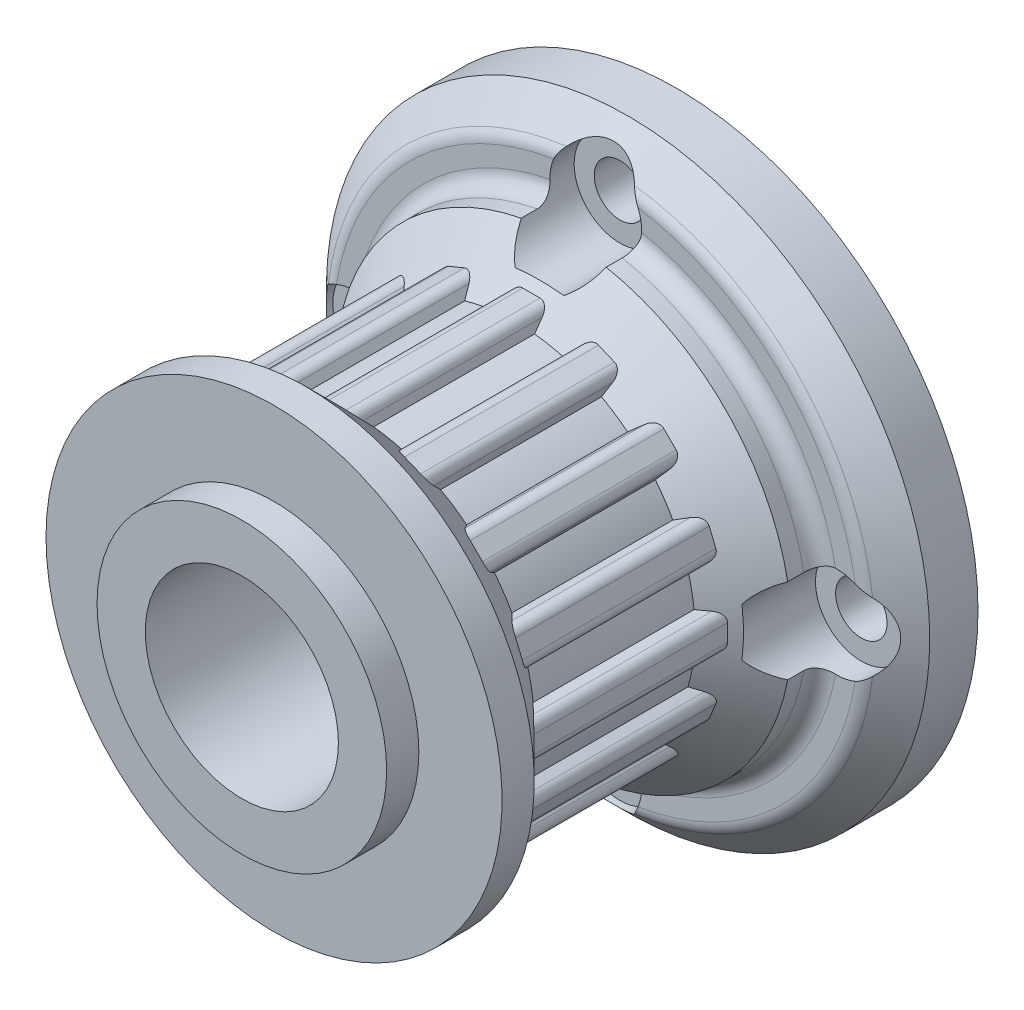
SolidWorks part; units mm, degrees
material "ABS"
ref_plane "Plan de face" through (0, 0, 0) normal (0, 0, 1) x (1, 0, 0)
ref_plane "Plan de dessus" through (0, 0, 0) normal (0, 1, 0) x (1, 0, 0)
ref_plane "Plan de droite" through (0, 0, 0) normal (1, 0, 0) x (0, 0, -1)
sketch "Esquisse5" plane through (0, 0, 0) normal (0, 0, 1) x (1, 0, 0)
  line L0 (0, 0) -> (0, 12.73) construction
  line L1 (0, 0) -> (4.8716, 11.761) construction
  line L2 (0, 12.1872) -> (0.5089, 12.1872)
  line L3 (1.1017, 11.6799) -> (1.2239, 10.8985)
  line L4 (1.2239, 10.8985) -> (2.9901, 10.5515)
  line L5 (2.9901, 10.5515) -> (3.3975, 11.2265)
  line L6 (4.1408, 11.4708) -> (4.6619, 11.2549)
  line L7 (0, 0) -> (2.107, 10.725) construction
  line L8 (4.6619, 11.2549) -> (5.1321, 11.0601)
  line L9 (5.4856, 10.3646) -> (5.2995, 9.5959)
  line L10 (5.2995, 9.5959) -> (6.7985, 8.5995)
  line L11 (6.7985, 8.5995) -> (7.4332, 9.0671)
  line L12 (8.2134, 9.0084) -> (8.6122, 8.6095)
  line L13 (8.6122, 8.6095) -> (8.9721, 8.2497)
  line L14 (9.0325, 7.4718) -> (8.5664, 6.8329)
  line L15 (8.5664, 6.8329) -> (9.57, 5.3386)
  line L16 (9.57, 5.3386) -> (10.3353, 5.5278)
  line L17 (11.0336, 5.1749) -> (11.2495, 4.6538)
  line L18 (11.2495, 4.6538) -> (11.4442, 4.1836)
  line L19 (11.2024, 3.4418) -> (10.5272, 3.03)
  line L20 (10.5272, 3.03) -> (10.8826, 1.2654)
  line L21 (10.8826, 1.2654) -> (11.6621, 1.1473)
  line L22 (12.1722, 0.554) -> (12.1722, -0.01)
  line L23 (12.1722, -0.01) -> (12.1722, -0.5189)
  line L24 (11.6649, -1.1117) -> (10.8835, -1.2339)
  line L25 (10.8835, -1.2339) -> (10.5365, -3.0001)
  line L26 (10.5365, -3.0001) -> (11.2115, -3.4075)
  line L27 (11.4558, -4.1508) -> (11.2399, -4.6719)
  line L28 (11.2399, -4.6719) -> (11.0452, -5.1421)
  line L29 (10.3496, -5.4957) -> (9.581, -5.3095)
  line L30 (9.581, -5.3095) -> (8.5845, -6.8085)
  line L31 (8.5845, -6.8085) -> (9.0522, -7.4432)
  line L32 (8.9934, -8.2234) -> (8.5946, -8.6222)
  line L33 (8.5946, -8.6222) -> (8.2347, -8.9821)
  line L34 (7.4568, -9.0425) -> (6.8179, -8.5764)
  line L35 (6.8179, -8.5764) -> (5.3236, -9.58)
  line L36 (5.3236, -9.58) -> (5.5128, -10.3453)
  line L37 (5.16, -11.0436) -> (4.6389, -11.2595)
  line L38 (4.6389, -11.2595) -> (4.1687, -11.4542)
  line L39 (3.4269, -11.2124) -> (3.015, -10.5372)
  line L40 (3.015, -10.5372) -> (1.2504, -10.8926)
  line L41 (1.2504, -10.8926) -> (1.1323, -11.6721)
  line L42 (0.5391, -12.1822) -> (-0.025, -12.1822)
  line L43 (-0.025, -12.1822) -> (-0.5339, -12.1822)
  line L44 (-1.1267, -11.6749) -> (-1.2489, -10.8935)
  line L45 (-1.2489, -10.8935) -> (-3.0151, -10.5465)
  line L46 (-3.0151, -10.5465) -> (-3.4225, -11.2215)
  line L47 (-4.1658, -11.4658) -> (-4.6869, -11.2499)
  line L48 (-4.6869, -11.2499) -> (-5.1571, -11.0552)
  line L49 (-5.5106, -10.3596) -> (-5.3245, -9.591)
  line L50 (-5.3245, -9.591) -> (-6.8235, -8.5945)
  line L51 (-6.8235, -8.5945) -> (-7.4582, -9.0622)
  line L52 (-8.2384, -9.0034) -> (-8.6372, -8.6046)
  line L53 (-8.6372, -8.6046) -> (-8.9971, -8.2447)
  line L54 (-9.0575, -7.4668) -> (-8.5914, -6.8279)
  line L55 (-8.5914, -6.8279) -> (-9.5949, -5.3336)
  line L56 (-9.5949, -5.3336) -> (-10.3603, -5.5228)
  line L57 (-11.0586, -5.17) -> (-11.2745, -4.6489)
  line L58 (-11.2745, -4.6489) -> (-11.4692, -4.1787)
  line L59 (-11.2274, -3.4369) -> (-10.5522, -3.025)
  line L60 (-10.5522, -3.025) -> (-10.9076, -1.2604)
  line L61 (-10.9076, -1.2604) -> (-11.6871, -1.1423)
  line L62 (-12.1972, -0.5491) -> (-12.1972, 0.015)
  line L63 (-12.1972, 0.015) -> (-12.1972, 0.5239)
  line L64 (-11.6899, 1.1167) -> (-10.9085, 1.2389)
  line L65 (-10.9085, 1.2389) -> (-10.5615, 3.0051)
  line L66 (-10.5615, 3.0051) -> (-11.2365, 3.4125)
  line L67 (-11.4808, 4.1558) -> (-11.2649, 4.6769)
  line L68 (-11.2649, 4.6769) -> (-11.0702, 5.1471)
  line L69 (-10.3746, 5.5006) -> (-9.6059, 5.3145)
  line L70 (-9.6059, 5.3145) -> (-8.6095, 6.8135)
  line L71 (-8.6095, 6.8135) -> (-9.0772, 7.4482)
  line L72 (-9.0184, 8.2284) -> (-8.6195, 8.6272)
  line L73 (-8.6195, 8.6272) -> (-8.2597, 8.9871)
  line L74 (-7.4818, 9.0475) -> (-6.8429, 8.5814)
  line L75 (-6.8429, 8.5814) -> (-5.3486, 9.5849)
  line L76 (-5.3486, 9.5849) -> (-5.5378, 10.3503)
  line L77 (-5.185, 11.0486) -> (-4.6638, 11.2645)
  line L78 (-4.6638, 11.2645) -> (-4.1937, 11.4592)
  line L79 (-3.4518, 11.2174) -> (-3.04, 10.5422)
  line L80 (-3.04, 10.5422) -> (-1.2754, 10.8975)
  line L81 (-1.2754, 10.8975) -> (-1.1573, 11.6771)
  line L82 (-0.5641, 12.1872) -> (0, 12.1872)
  circle A0 centre (0, 0) radius 12.73 construction
  circle A1 centre (0, 0) radius 12.23 construction
  circle A2 centre (0, 0) radius 10.93 construction
  arc A3 (4.1408, 11.4708) -> (3.3975, 11.2265) centre (3.9112, 10.9164) ccw
  arc A4 (1.1017, 11.6799) -> (0.5089, 12.1872) centre (0.5089, 11.5872) ccw
  arc A5 (8.2134, 9.0084) -> (7.4332, 9.0671) centre (7.7891, 8.5841) ccw
  arc A6 (5.4856, 10.3646) -> (5.1321, 11.0601) centre (4.9025, 10.5058) ccw
  arc A7 (11.0336, 5.1749) -> (10.3353, 5.5278) centre (10.4793, 4.9453) ccw
  arc A8 (9.0325, 7.4718) -> (8.9721, 8.2497) centre (8.5478, 7.8254) ccw
  arc A9 (12.1722, 0.554) -> (11.6621, 1.1473) centre (11.5722, 0.554) ccw
  arc A10 (11.2024, 3.4418) -> (11.4442, 4.1836) centre (10.8899, 3.954) ccw
  arc A11 (11.4558, -4.1508) -> (11.2115, -3.4075) centre (10.9015, -3.9212) ccw
  arc A12 (11.6649, -1.1117) -> (12.1722, -0.5189) centre (11.5722, -0.5189) ccw
  arc A13 (8.9934, -8.2234) -> (9.0522, -7.4432) centre (8.5691, -7.7991) ccw
  arc A14 (10.3496, -5.4957) -> (11.0452, -5.1421) centre (10.4908, -4.9125) ccw
  arc A15 (5.16, -11.0436) -> (5.5128, -10.3453) centre (4.9304, -10.4893) ccw
  arc A16 (7.4568, -9.0425) -> (8.2347, -8.9821) centre (7.8104, -8.5578) ccw
  arc A17 (0.5391, -12.1822) -> (1.1323, -11.6721) centre (0.5391, -11.5822) ccw
  arc A18 (3.4269, -11.2124) -> (4.1687, -11.4542) centre (3.9391, -10.8999) ccw
  arc A19 (-4.1658, -11.4658) -> (-3.4225, -11.2215) centre (-3.9362, -10.9115) ccw
  arc A20 (-1.1267, -11.6749) -> (-0.5339, -12.1822) centre (-0.5339, -11.5822) ccw
  arc A21 (-8.2384, -9.0034) -> (-7.4582, -9.0622) centre (-7.8141, -8.5792) ccw
  arc A22 (-5.5106, -10.3596) -> (-5.1571, -11.0552) centre (-4.9275, -10.5009) ccw
  arc A23 (-11.0586, -5.17) -> (-10.3603, -5.5228) centre (-10.5043, -4.9404) ccw
  arc A24 (-9.0575, -7.4668) -> (-8.9971, -8.2447) centre (-8.5728, -7.8204) ccw
  arc A25 (-12.1972, -0.5491) -> (-11.6871, -1.1423) centre (-11.5972, -0.5491) ccw
  arc A26 (-11.2274, -3.4369) -> (-11.4692, -4.1787) centre (-10.9149, -3.9491) ccw
  arc A27 (-11.4808, 4.1558) -> (-11.2365, 3.4125) centre (-10.9264, 3.9262) ccw
  arc A28 (-11.6899, 1.1167) -> (-12.1972, 0.5239) centre (-11.5972, 0.5239) ccw
  arc A29 (-9.0184, 8.2284) -> (-9.0772, 7.4482) centre (-8.5941, 7.8041) ccw
  arc A30 (-10.3746, 5.5006) -> (-11.0702, 5.1471) centre (-10.5158, 4.9175) ccw
  arc A31 (-5.185, 11.0486) -> (-5.5378, 10.3503) centre (-4.9553, 10.4943) ccw
  arc A32 (-7.4818, 9.0475) -> (-8.2597, 8.9871) centre (-7.8354, 8.5628) ccw
  arc A33 (-0.5641, 12.1872) -> (-1.1573, 11.6771) centre (-0.5641, 11.5872) ccw
  arc A34 (-3.4518, 11.2174) -> (-4.1937, 11.4592) centre (-3.964, 10.9049) ccw
  circle A36 centre (0, 0) radius 6
  point P15 (3.6641, 11.6682)
  point P19 (1.0224, 12.1872)
  point P172 (-0.0125, 0.0025)
  dimension "D1" = 25.46
  dimension "D8" = 0.6
  dimension "D10" = 12
  dimension "D2" = 22.5
  dimension "D3" = 0.5
  dimension "D4" = 1.3
  dimension "D5" = 20
  dimension "D6" = 20
  dimension "D7" = 1.8
  dimension "D9" = 16
sketch "Esquisse11" plane through (0, 0, 0) normal (0, 0, 1) x (1, 0, 0)
  line L0 (0, 15) -> (0, 0) construction
  line L1 (15, 0) -> (0, 0) construction
  line L2 (0, 0) -> (-15, 0) construction
  line L3 (0, 0) -> (0, -15) construction
  circle A1 centre (0, 0) radius 15 construction
  circle A2 centre (0, 0) radius 18.75
  circle A6 centre (-15, 0) radius 1.6
  circle A7 centre (0, 15) radius 1.6
  circle A8 centre (15, 0) radius 1.6
  circle A9 centre (0, -15) radius 1.6
  point P3 (0, 0)
  point P6 (0, -15)
  point P8 (15, 0)
  point P10 (-15, 0)
  dimension "D2" = 3.2
  dimension "D3" = 3.2
  dimension "D4" = 3.2
  dimension "D5" = 3.2
  dimension "D6" = 30
  dimension "D1" = 37.5
extrude "Boss.-Extru.4" add sketch "Esquisse11" along normal blind 5
extrude "Boss.-Extru.5" add sketch "Esquisse5" along normal blind 24
sketch "Esquisse12" plane through (0, 0, 5) normal (0, 0, 1) x (1, 0, 0)
  circle A0 centre (0, 0) radius 1.6
  dimension "D1" = 3.2
extrude "Enlèv. mat.-Extru.7" cut sketch "Esquisse12" against normal blind 32
sketch "Esquisse13" plane through (0, 0, 0) normal (0, 1, 0) x (1, 0, 0)
  line L0 (0, 0) -> (0, -25.2892) construction
  line L1 (18.75, 0) -> (-18.75, 0) construction
  line L2 (6, -5) -> (6, -25)
  line L3 (6, -25) -> (14.1722, -25)
  line L4 (14.1722, -25) -> (14.1722, -23)
  line L5 (14.1722, -23) -> (11.1722, -20)
  line L6 (11.1722, -20) -> (11.1722, -10)
  line L7 (11.1722, -10) -> (14.1722, -7)
  line L8 (14.1722, -7) -> (14.1722, -5)
  line L9 (14.1722, -5) -> (6, -5)
  line L10 (12.1722, -24) -> (12.1722, -5) construction
  point P14 (13.6851, -23)
  dimension "D1" = 6
  dimension "D2" = 2
  dimension "D3" = 2
  dimension "D4" = 45
  dimension "D5" = 45
  dimension "D6" = 10
  dimension "D8" = 5
  dimension "D9" = 2
  dimension "D10" = 20
revolve "Révolution1" add sketch "Esquisse13" angle 360 about L0
sketch "Esquisse15" plane through (0, 0, 5) normal (0, 0, 1) x (1, 0, 0)
  circle A8 centre (15, 0) radius 2.85
  circle A9 centre (0, 15) radius 2.85
  circle A10 centre (0, -15) radius 2.85
  circle A11 centre (-15, 0) radius 2.85
extrude "Enlèv. mat.-Extru.9" cut sketch "Esquisse15" against normal blind 1.5 and the other way blind 3.5
chamfer "Chanfrein1" distance 2 angle 45 1 edges at (18.75, 0, 5)
fillet "Congé1" radius 1 8 edges at (10.0213, 10.0213, 5) (-10.0213, 10.0213, 5) (-10.0213, -10.0213, 5) (10.0213, -10.0213, 5) (11.844, 11.844, 5) (11.844, -11.844, 5) (-11.844, -11.844, 5) (-11.844, 11.844, 5)
sketch "Esquisse16" plane through (0, 0, 25) normal (0, 0, 1) x (1, 0, 0)
  circle A0 centre (0, 0) radius 6 construction
  circle A1 centre (0, 0) radius 6
  circle A2 centre (0, 0) radius 9
  dimension "D1" = 18
extrude "Boss.-Extru.6" add sketch "Esquisse16" along normal blind 2
equation "\"A\"= 26"
equation "\"E\"= 20.5"
equation "\"C\"= 6"
equation "\"B\"= 16.5"
equation "\"Dp\"= 25.46'Diamètre primitif"
equation "\"Df\"= 28'Diamètre extérieur"
equation "\"Teeth\"= 16'Nombre de dents"
equation "\"L\"= 15'Largeur courroie"
equation "\"D1@Enlèv. mat.-Extru.1\"=\"A\"-\"E\"-2"
equation "\"D1@Esquisse3\"=\"L\"+2"
equation "\"D2@Esquisse3\"=\"Dp\"/2-5"
equation "\"D1@Esquisse5\"=\"Dp\""
equation "\"D2@Esquisse5\"=360/\"Teeth\""
